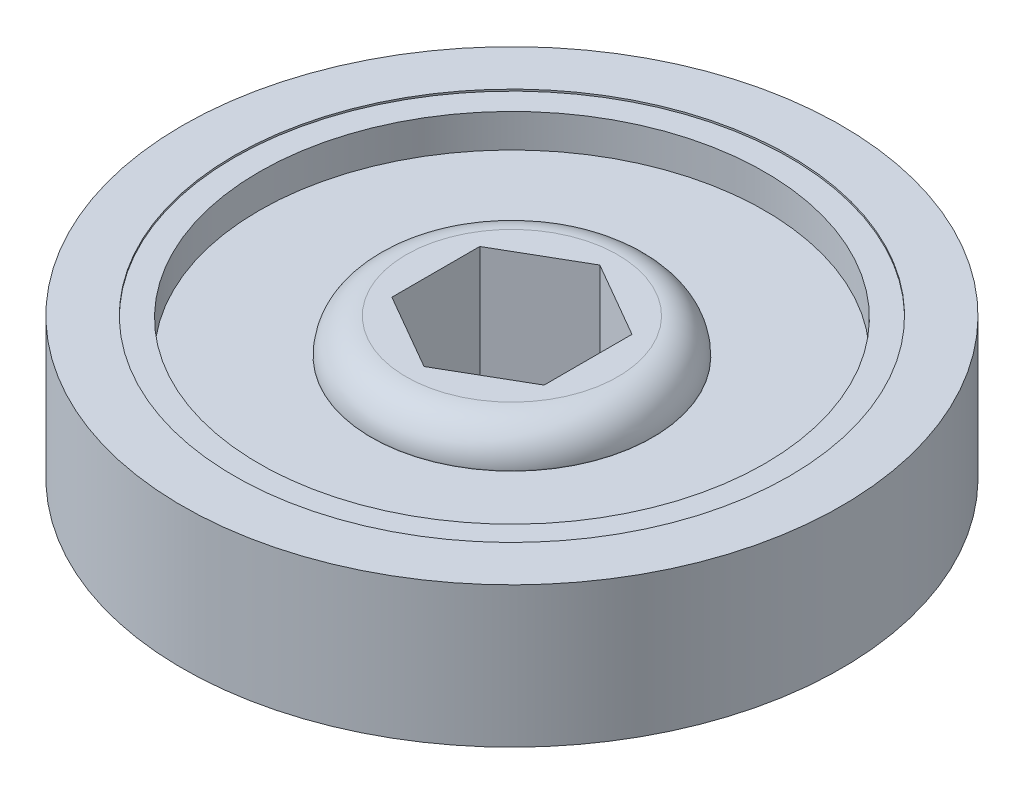
SolidWorks part; units mm, degrees
material "PE High Density"
ref_plane "Front Plane" through (0, 0, 0) normal (0, 0, 1) x (1, 0, 0)
ref_plane "Top Plane" through (0, 0, 0) normal (0, 1, 0) x (1, 0, 0)
ref_plane "Right Plane" through (0, 0, 0) normal (1, 0, 0) x (0, 0, -1)
sketch "Sketch2" plane through (0, 0, 0) normal (0, 0, 1) x (1, 0, 0)
  line L0 (0, 0) -> (23.8125, 0) construction
  line L1 (0, 0) -> (7.6454, 0)
  line L2 (10.16, -2.5146) -> (10.16, -2.54)
  line L3 (10.16, -2.54) -> (18.2628, -2.54)
  line L4 (18.2628, -2.54) -> (18.2628, -0.127)
  line L5 (18.2628, -0.127) -> (20.0609, -0.127)
  line L6 (20.0609, -0.127) -> (20.0609, 0)
  line L7 (20.0609, 0) -> (23.8125, 0)
  line L8 (0, 0) -> (0, -10.16) construction
  line L9 (0, -5.08) -> (23.8125, -5.08) construction
  line L10 (0, -10.16) -> (23.8125, -10.16) construction
  line L11 (20.0609, -10.16) -> (23.8125, -10.16)
  line L12 (20.0609, -10.033) -> (20.0609, -10.16)
  line L13 (18.2628, -10.033) -> (20.0609, -10.033)
  line L14 (18.2628, -7.62) -> (18.2628, -10.033)
  line L15 (10.16, -7.62) -> (18.2628, -7.62)
  line L16 (10.16, -7.6454) -> (10.16, -7.62)
  line L17 (0, -10.16) -> (7.6454, -10.16)
  line L18 (23.8125, 0) -> (23.8125, -10.16)
  line L19 (0, 0) -> (0, -10.16)
  arc A0 (7.6454, 0) -> (10.16, -2.5146) centre (7.6454, -2.5146) cw
  arc A1 (7.6454, -10.16) -> (10.16, -7.6454) centre (7.6454, -7.6454) ccw
  point P14 (10.16, 0)
  point P24 (10.16, -10.16)
  dimension "D6" = 2.5146
  dimension "D1" = 23.8125
  dimension "D2" = 10.16
  dimension "D3" = 2.54
  dimension "D4" = 10.16
  dimension "D5" = 0.127
revolve "Revolve1" add sketch "Sketch2" angle 360 about L19
sketch "Sketch3" plane through (0, 0, 0) normal (0, 1, 0) x (1, 0, 0)
  line L1 (0, 6.35) -> (-5.4993, 3.175)
  line L2 (-5.4993, 3.175) -> (-5.4993, -3.175)
  line L3 (-5.4993, -3.175) -> (0, -6.35)
  line L4 (0, -6.35) -> (5.4993, -3.175)
  line L5 (5.4993, -3.175) -> (5.4993, 3.175)
  line L6 (5.4993, 3.175) -> (0, 6.35)
  circle A0 centre (0, 0) radius 6.35 construction
extrude "Cut-Extrude1" cut sketch "Sketch3" against normal through all
